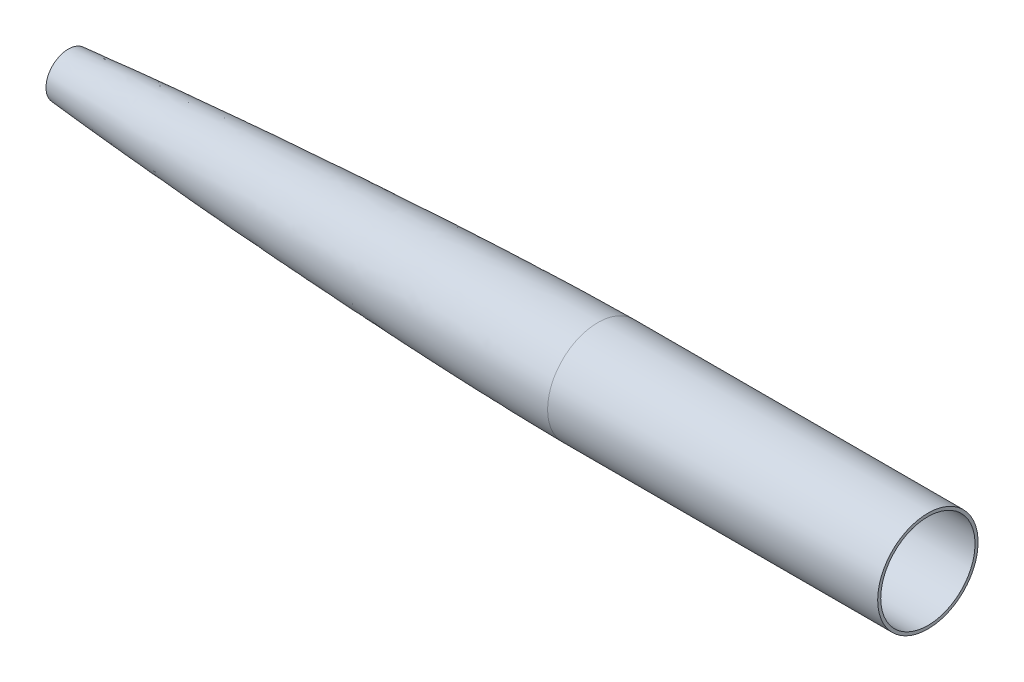
SolidWorks part; units mm, degrees
ref_plane "Front Plane" through (0, 0, 0) normal (0, 0, 1) x (1, 0, 0)
ref_plane "Top Plane" through (0, 0, 0) normal (0, 1, 0) x (1, 0, 0)
ref_plane "Right Plane" through (0, 0, 0) normal (1, 0, 0) x (0, 0, -1)
sketch "Sketch1" plane through (0, 0, 0) normal (0, 0, 1) x (1, 0, 0)
  line L0 (381, 27.051) -> (558.8, 27.051)
  line L1 (0, 0) -> (558.8, 0)
  line L2 (558.8, 0) -> (558.8, 27.051)
  spline S0 degree 4 poles (0, 0) (0.0018, 0.0033) (0.0061, 0.0095) (0.0171, 0.02) (0.0412, 0.0382) (0.0764, 0.0602) (0.1228, 0.0854) (0.1888, 0.1177) (0.2679, 0.1528) (0.3871, 0.2016) (0.5655, 0.2679) (0.8266, 0.3563) (1.2535, 0.4872) (1.9699, 0.6847) (3.2511, 0.9983) (5.6282, 1.5081) (10.1301, 2.3429) (18.2315, 3.6284) (31.4818, 5.4267) (49.3274, 7.5151) (70.6558, 9.7196) (93.8412, 11.8743) (117.0428, 13.8452) (140.2568, 15.6631) (163.481, 17.3469) (186.7137, 18.9085) (209.9538, 20.3548) (239.0123, 22.023) (268.081, 23.5052) (297.159, 24.7943) (326.2459, 25.8608) (346.181, 26.4563) (362.7795, 26.8367) (373.5599, 26.9977) (378.5199, 27.0448) (381, 27.051) knots 0 0 0 0 0 0.000039 0.000079 0.000158 0.000316 0.000473 0.000631 0.000926 0.001221 0.001821 0.002622 0.003809 0.005893 0.009595 0.016421 0.029243 0.053793 0.095411 0.156317 0.217224 0.27813 0.339037 0.399944 0.46085 0.521757 0.582663 0.64357 0.765383 0.826289 0.887196 0.948102 0.974051 1 1 1 1 1 construction
  spline S1 degree 4 poles (0, 0) (0.0018, 0.0033) (0.0061, 0.0095) (0.0171, 0.02) (0.0412, 0.0382) (0.0764, 0.0602) (0.1228, 0.0854) (0.1888, 0.1177) (0.2679, 0.1528) (0.3871, 0.2016) (0.5655, 0.2679) (0.8266, 0.3563) (1.2535, 0.4872) (1.9699, 0.6847) (3.2511, 0.9983) (5.6282, 1.5081) (10.1301, 2.3429) (18.2315, 3.6284) (31.4818, 5.4267) (49.3274, 7.5151) (70.6558, 9.7196) (93.8412, 11.8743) (117.0428, 13.8452) (140.2568, 15.6631) (163.481, 17.3469) (186.7137, 18.9085) (209.9538, 20.3548) (239.0123, 22.023) (268.081, 23.5052) (297.159, 24.7943) (326.2459, 25.8608) (346.181, 26.4563) (362.7795, 26.8367) (373.5599, 26.9977) (378.5199, 27.0448) (381, 27.051) knots 0 0 0 0 0 0.000039 0.000079 0.000158 0.000316 0.000473 0.000631 0.000926 0.001221 0.001821 0.002622 0.003809 0.005893 0.009595 0.016421 0.029243 0.053793 0.095411 0.156317 0.217224 0.27813 0.339037 0.399944 0.46085 0.521757 0.582663 0.64357 0.765383 0.826289 0.887196 0.948102 0.974051 1 1 1 1 1
  dimension "D1" = 381
  dimension "D2" = 177.8
revolve "Revolve1" add sketch "Sketch1" angle 360 about L1
shell "Shell1" thickness 1.651 removed face at (558.8, 0, 27.051)
ref_plane "Plane1" through (95.758, 0, 0) normal (1, 0, 0) x (0, 0, -1)
split "Split1" trim tools "Plane1" bodies to split 101 resulting bodies 103
